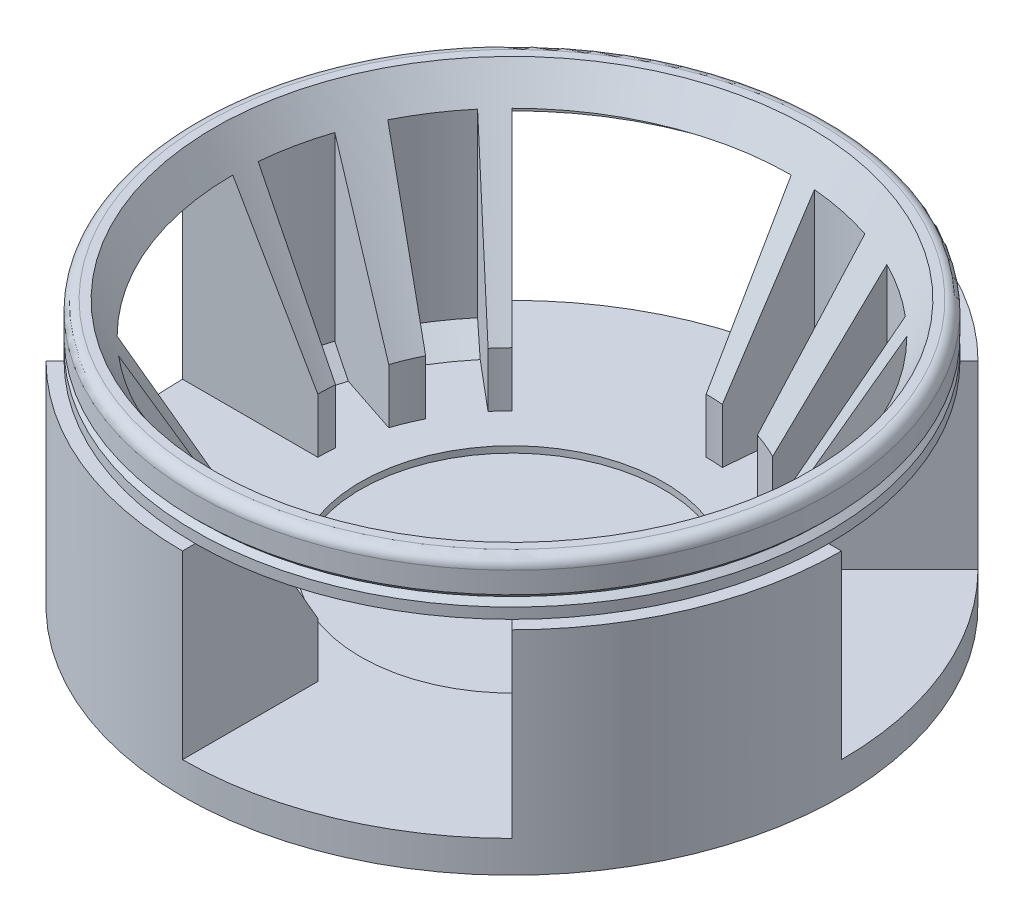
SolidWorks part; units mm, degrees
ref_plane "前视基准面" through (0, 0, 0) normal (0, 0, 1) x (1, 0, 0)
ref_plane "上视基准面" through (0, 0, 0) normal (0, 1, 0) x (1, 0, 0)
ref_plane "右视基准面" through (0, 0, 0) normal (1, 0, 0) x (0, 0, -1)
sketch "草图1" plane through (0, 0, 0) normal (0, 1, 0) x (1, 0, 0)
  circle A0 centre (0, 0) radius 31
  dimension "D1" = 62
extrude "凸台-拉伸1" add sketch "草图1" along normal blind 3
sketch "草图2" plane through (0, 3, 0) normal (0, 1, 0) x (1, 0, 0)
  line L0 (0, 28) -> (0, 31)
  line L1 (19.799, 19.799) -> (21.9203, 21.9203)
  line L2 (19.799, -19.799) -> (21.9203, -21.9203)
  line L3 (28, 0) -> (31, 0)
  line L4 (-19.799, -19.799) -> (-22.6274, -22.6274)
  line L5 (0, -28) -> (0, -31)
  line L6 (-19.799, 19.799) -> (-21.9203, 21.9203)
  line L7 (-28, 0) -> (-31, 0)
  circle A0 centre (0, 0) radius 31
  circle A1 centre (0, 0) radius 28
  circle A2 centre (0, 0) radius 31 construction
  point P21 (0, 0)
  circle M3 centre (0, 0) radius 31
  dimension "D1" = 3
  dimension "D2" = 4
extrude "凸台-拉伸2" add sketch "草图2" along normal blind 22 contours A1 L1 L0 M3 | A1 L6 L7 M3 | A1 L4 L5 M3 | A1 L2 L3 M3 region at (11.0107, 3, -26.5822) region at (-26.5822, 3, -11.0107) region at (26.5822, 3, 11.0107) region at (-11.0107, 3, 26.5822)
sketch "草图3" plane through (0, 3, 0) normal (0, 1, 0) x (1, 0, 0)
  circle A0 centre (0, 0) radius 14.25
  dimension "D1" = 28.5
extrude "切除-拉伸1" cut sketch "草图3" against normal blind 0.6
sketch "草图4" plane through (0, 25, 0) normal (0, 1, 0) x (1, 0, 0)
  circle A0 centre (0, 0) radius 31
  circle A1 centre (0, 0) radius 29.8
  arc A3 (21.9203, -21.9203) -> (31, 0) centre (0, 0) ccw construction
  dimension "D1" = 1.2
extrude "切除-拉伸2" cut sketch "草图4" against normal blind 5
fillet "圆角1" radius 1 4 edges at (-27.5316, 25, -11.404) (11.404, 25, -27.5316) (27.5316, 25, 11.404) (-11.404, 25, 27.5316)
chamfer "倒角1" distance 22 angle 30 4 edges at (-10.7151, 3, 25.8686) (25.8686, 3, 10.7151) (10.7151, 3, -25.8686) (-25.8686, 3, -10.7151) first distance on face at (-10.3073, 14, 24.8841) first distance on face at (24.8841, 14, 10.3073) first distance on face at (10.3073, 14, -24.8841) first distance on face at (-24.8841, 14, -10.3073)
sketch "草图5" plane through (0, 0, 0) normal (0.7071, 0, 0.7071) x (0.7071, 0, -0.7071)
  line L0 (26.2679, 22) -> (28, 25)
  line L2 (28, 25) -> (28.8, 25)
  line L3 (29.8, 24) -> (29.8, 20) construction
  line L4 (29.8, 24) -> (29.8, 20)
  line L5 (27.4226, 22) -> (27.8431, 22.7283)
  line L6 (28.8, 21.2) -> (28.8, 22.4719)
  line L7 (28.8, 21.2) -> (28.8, 20)
  line L8 (26.2679, 22) -> (27.4226, 22)
  line L9 (26.6573, 20.6743) -> (28.5774, 24) construction
  line L10 (25.7912, 21.1743) -> (28, 25) construction
  line L11 (28.8, 20) -> (29.8, 20)
  line L12 (28.5774, 24) -> (28.8, 24) construction
  line L13 (28.8, 24) -> (28.8, 20) construction
  line L15 (0, 0) -> (0, 38.1577) construction
  arc A0 (29.8, 24) -> (28.8, 25) centre (28.8, 24) ccw construction
  arc A1 (29.8, 24) -> (28.8, 25) centre (28.8, 24) ccw
  arc A2 (28.8, 22.4719) -> (27.8431, 22.7283) centre (28.2872, 22.4719) ccw
  arc A3 (28.8, 24) -> (28.8, 24) centre (28.8, 24) ccw construction
  dimension "D2" = 3
  dimension "D1" = 1
revolve "旋转1" add sketch "草图5" angle 360 about L15
sketch "草图6" plane through (0, 25, 0) normal (0, 1, 0) x (1, 0, 0)
  line L0 (0, 15.2983) -> (0, 26.2679)
  line L1 (1.3333, 15.2401) -> (2.2894, 26.168)
  line L2 (10.8175, 10.8175) -> (18.5742, 18.5742)
  line L3 (9.8336, 11.7192) -> (16.8847, 20.1224)
  line L4 (10.8175, -10.8175) -> (18.5742, -18.5742)
  line L5 (11.7192, -9.8336) -> (20.1224, -16.8847)
  line L6 (6.8659, 13.6711) -> (11.789, 23.4739)
  line L7 (4.812, 14.5218) -> (8.2624, 24.9347)
  line L8 (13.6711, -6.8659) -> (23.4739, -11.789)
  line L9 (14.5218, -4.812) -> (24.9347, -8.2624)
  line L10 (15.2401, -1.3333) -> (26.168, -2.2894)
  line L11 (15.2983, 0) -> (26.2679, 0)
  line L12 (-10.8175, -10.8175) -> (-18.5742, -18.5742)
  line L13 (-9.8336, -11.7192) -> (-16.8847, -20.1224)
  line L14 (-6.8659, -13.6711) -> (-11.789, -23.4739)
  line L15 (-4.812, -14.5218) -> (-8.2624, -24.9347)
  line L16 (-19.5473, -17.5473) -> (-19.5742, -17.5742)
  line L17 (-1.3333, -15.2401) -> (-2.2894, -26.168)
  line L18 (0, -15.2983) -> (0, -26.2679)
  line L19 (-10.8175, 10.8175) -> (-18.5742, 18.5742)
  line L20 (-11.7192, 9.8336) -> (-20.1224, 16.8847)
  line L21 (-13.6711, 6.8659) -> (-23.4739, 11.789)
  line L22 (-14.5218, 4.812) -> (-24.9347, 8.2624)
  line L23 (-15.2401, 1.3333) -> (-26.168, 2.2894)
  line L24 (-15.2983, 0) -> (-26.2679, 0)
  line L32 (-18.0675, 19.0675) -> (-18.5742, 19.5742) [skipped]
  line L33 (-19.6215, 17.4644) -> (-20.1224, 17.8847) [skipped]
  line L35 (-23.0592, 12.5808) -> (-23.4739, 12.789) [skipped]
  line L36 (-26.2489, 1) -> (-26.2679, 1) [skipped]
  line L37 (-26.0623, 3.2802) -> (-26.168, 3.2894) [skipped]
  line L39 (-24.6198, 9.1581) -> (-24.9347, 9.2624) [skipped]
  line L40 (-1, -14.2983) -> (-1, -15.2656) [skipped]
  line L41 (-2.3333, -14.2401) -> (-2.4092, -15.1074) [skipped]
  line L43 (-5.812, -13.5218) -> (-5.9952, -14.0746) [skipped]
  line L44 (-7.8659, -12.6711) -> (-8.039, -13.0158) [skipped]
  line L46 (-10.8336, -10.7192) -> (-10.871, -10.7638) [skipped]
  line L47 (14.2983, 0) -> (15.2983, 0) [skipped]
  line L48 (14.2401, -1.3333) -> (15.2322, -1.4201) [skipped]
  line L49 (9.8175, -10.8175) -> (10.306, -11.306) [skipped]
  line L50 (10.7192, -9.8336) -> (11.2956, -10.3173) [skipped]
  line L52 (12.6711, -6.8659) -> (13.4637, -7.264) [skipped]
  line L53 (13.5218, -4.812) -> (14.4198, -5.1096) [skipped]
  circle A0 centre (0, 0) radius 26.2679
  circle A1 centre (0, 0) radius 15.2983
  point P60 (0, 0)
  point P74 (-0.5, 0.5)
  point P123 (0, 0)
  dimension "D1" = 5
  dimension "D2" = 5
  dimension "D3" = 4
  dimension "D7" = 4
extrude "切除-拉伸3" cut sketch "草图6" against normal up to surface (22 mm away) contours A1 L7 A0 L1 | A1 L3 A0 L6 | A1 L9 A0 L10 | A1 L5 A0 L8 | A1 L15 A0 L17 | A1 L13 A0 L14 | A1 L22 A0 L23 | A1 L20 A0 L21 region at (4.2906, 25, -20.7793) region at (-17.7271, 25, -11.6593) region at (11.6593, 25, -17.7271) region at (-20.7793, 25, -4.2906) region at (20.7793, 25, 4.2906) region at (-11.6593, 25, 17.7271) region at (17.7271, 25, 11.6593) region at (-4.2906, 25, 20.7793) up to face at (0, 3, 14.25)
sketch "草图7" plane through (0, 25, 0) normal (0, 1, 0) x (1, 0, 0)
  circle A0 centre (0, 0) radius 18.2679
  arc A1 (26.2679, 0) -> (18.5742, 18.5742) centre (0, 0) ccw construction
  dimension "D1" = 8
extrude "切除-拉伸4" cut sketch "草图7" against normal up to surface (22 mm away) up to face at (0, 3, 14.25)
sketch "草图9" plane through (0, 0, 0) normal (0, 0, 1) x (1, 0, 0)
  line L0 (29.8, 22) -> (29.3, 21.5)
  line L1 (29.8, 20) -> (29.8, 24) construction
  line L2 (29.3, 21.5) -> (29.8, 21)
  line L4 (29.8, 20) -> (21.0718, 20) construction
  line L6 (0, 0) -> (0, 33.755) construction
  line L7 (29.8, 22) -> (29.8, 21)
  line L8 (31, 20) -> (21.9203, 20) construction
  dimension "D1" = 45
  dimension "D2" = 45
  dimension "D3" = 1
  dimension "D4" = 1
revolve "切除-旋转1" cut sketch "草图9" angle 360 about L6
chamfer "倒角2" distance 2 angle 45 8 edges at (-5.3118, 3, 25.7253) (-14.4345, 3, 21.9466) (21.9466, 3, 14.4345) (25.7253, 3, 5.3118) (5.3118, 3, -25.7253) (14.4345, 3, -21.9466) (-25.7253, 3, -5.3118) (-21.9466, 3, -14.4345)
